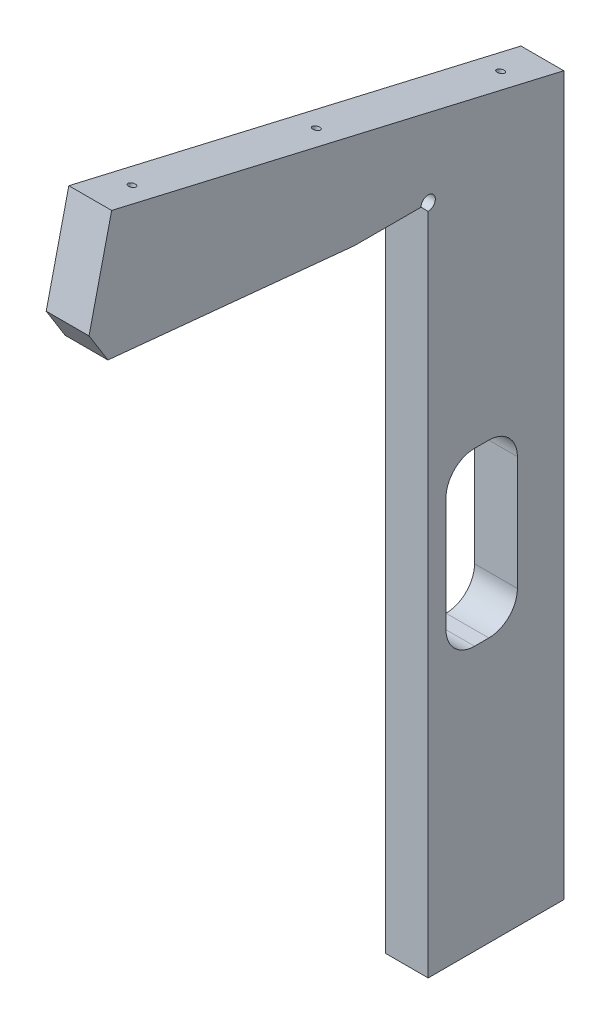
SolidWorks part; units mm, degrees
material "MDF"
ref_plane "Front Plane" through (0, 0, 0) normal (0, 0, 1) x (1, 0, 0)
ref_plane "Top Plane" through (0, 0, 0) normal (0, 1, 0) x (1, 0, 0)
ref_plane "Right Plane" through (0, 0, 0) normal (1, 0, 0) x (0, 0, -1)
sketch "Sketch2" plane through (-113.7888, 0, 0) normal (1, 0, 0) x (0, 0, -1)
  line L17 (0, 20.8246) -> (-83.8286, 40.3069)
  line L18 (0, 20.8246) -> (-83.8286, 40.3069)
  line L29 (-83.8286, 40.3069) -> (-93.1962, 0)
  line L30 (-83.8286, 40.3069) -> (-93.1962, 0)
  line L31 (-93.1962, 0) -> (-63.5, 0)
  line L32 (-93.1962, 0) -> (-63.5, 0)
  line L46 (0, -298.45) -> (-60.325, -298.45)
  line L47 (0, -392.9838) -> (0, -398.937) construction
  line L48 (-28.575, -298.45) -> (0, -298.45) construction
  line L53 (-8.8658, -437.642) -> (0, -437.642)
  line L55 (0, -437.642) -> (0, 20.8246)
  line L57 (-60.325, -3.175) -> (-60.325, -412.75)
  line L60 (0, -298.45) -> (0, 20.8246)
  line L62 (-60.325, -3.175) -> (-60.325, -298.45)
  arc A14 (-60.325, -3.175) -> (-63.5, 0) centre (-60.325, 0) ccw
  arc A15 (-60.325, -412.75) -> (-8.8658, -437.642) centre (-28.575, -412.75) ccw
  arc A17 (-60.325, -3.175) -> (-63.5, 0) centre (-60.325, 0) ccw
  dimension "D2" = 0
extrude "Boss-Extrude1" add sketch "Sketch2" along normal blind 19.05
sketch "Sketch3" plane through (-113.7888, 0, 0) normal (-1, 0, 0) x (0, 0, 1)
  line L0 (83.8286, 40.3069) -> (201.0857, 67.5582)
  line L1 (495.3358, 135.9439) -> (66.675, 36.3203) construction
  line L2 (201.0857, 67.5582) -> (214.0229, 11.8918)
  line L7 (83.8286, 40.3069) -> (93.1962, 0)
  line L8 (93.1962, 0) -> (214.0229, 11.8918)
  arc A0 (63.5, 0) -> (60.325, -3.175) centre (60.325, 0) ccw construction
  dimension "D1" = 57.15
  dimension "D2" = 152.4
extrude "Boss-Extrude2" add sketch "Sketch3" against normal through all
chamfer "Chamfer1" distance 12.7 angle 45 1 edges at (-104.2638, 11.8918, 214.0229) first distance on face at (-104.2638, 39.725, 207.5543)
hole_wizard "Hole3" positions "Sketch8" profile "Sketch9" legacy
sketch "Sketch8" plane through (0, 45.0826, -35.8775) normal (0, 0.974, -0.2264) x (-1, 0, 0)
  line L0 (218.5638, 29.4548) -> (218.5638, 115.5175) construction
  line L4 (202.6895, 537.9919) -> (202.6895, 97.9067) construction
  line L9 (88.3895, 537.9919) -> (88.3895, 97.9067) construction
  line L13 (104.2638, 29.4548) -> (104.2638, 235.8996) construction
  line L16 (0, 537.9919) -> (0, 29.4548) construction
  point P0 (218.5638, 102.8175)
  point P2 (218.5638, 48.5048)
  point P33 (202.6895, 123.3067)
  point P35 (202.6895, 317.9493)
  point P37 (202.6895, 518.9419)
  point P51 (88.3895, 518.9419)
  point P53 (88.3895, 317.9493)
  point P55 (88.3895, 123.3067)
  point P69 (104.2638, 216.8496)
  point P71 (104.2638, 132.6772)
  point P73 (104.2638, 48.5048)
  point P83 (-104.2638, 48.5048)
  point P84 (-104.2638, 132.6772)
  point P85 (-104.2638, 216.8496)
  point P86 (-88.3895, 123.3067)
  point P87 (-88.3895, 317.9493)
  point P88 (-88.3895, 518.9419)
  point P89 (-202.6895, 518.9419)
  point P90 (-202.6895, 317.9493)
  point P91 (-202.6895, 123.3067)
  point P92 (-218.5638, 48.5048)
  point P93 (-218.5638, 102.8175)
sketch "Sketch9" plane through (-218.5638, 68.3578, 64.2709) normal (1, 0, 0) x (0, 0.2264, 0.974)
  line L0 (0, 0) -> (0, 51.7539)
  line L1 (0, 51.7539) -> (1.5875, 50.8)
  line L2 (1.5875, 50.8) -> (1.5875, 4.0177)
  line L3 (1.5875, 4.0177) -> (5.08, 0)
  line L4 (5.08, 0) -> (0, 0)
  line L5 (0, -14.3089) -> (0, 102.4216) construction
  line L6 (0, 51.7539) -> (-1.5875, 50.8) construction
  line L7 (-1.5875, 4.0177) -> (-5.08, 0) construction
  dimension "Diameter" = 3.175
  dimension "Depth" = 50.8
  dimension "C-Sink Diameter" = 10.16
  dimension "C-Sink Angle" = 82
  dimension "Drill Angle" = 118
hole_wizard "Hole4" positions "Sketch10" profile "Sketch11" legacy
sketch "Sketch10" plane through (0, 0, -25.4) normal (0, 0, -1) x (-1, 0, 0)
  line L0 (218.5638, 0) -> (218.5638, -437.642) construction
  line L4 (104.2638, 0) -> (104.2638, -298.45) construction
  line L13 (120.1388, -460.375) -> (120.1388, -311.15) construction
  line L16 (126.4888, -311.15) -> (113.7888, -311.15) construction
  line L18 (126.4888, -304.8) -> (-126.4888, -304.8) construction
  line L22 (94.7388, -276.225) -> (-94.7388, -276.225) construction
  line L24 (-94.7388, -285.75) -> (-94.7388, -266.7) construction
  line L26 (94.7388, -285.75) -> (94.7388, -266.7) construction
  line L27 (-94.7388, 0) -> (-94.7388, -19.05) construction
  line L29 (94.7388, 0) -> (94.7388, -19.05) construction
  line L31 (94.7388, -9.525) -> (-94.7388, -9.525) construction
  point P15 (218.5638, -31.75)
  point P17 (218.5638, -218.821)
  point P19 (218.5638, -418.592)
  point P28 (104.2638, -19.05)
  point P30 (104.2638, -149.225)
  point P32 (104.2638, -279.4)
  point P69 (120.1388, -330.2)
  point P71 (120.1388, -441.325)
  point P76 (-120.1388, -441.325)
  point P77 (-120.1388, -330.2)
  point P80 (-104.2638, -279.4)
  point P81 (-104.2638, -149.225)
  point P82 (-104.2638, -19.05)
  point P83 (-218.5638, -418.592)
  point P84 (-218.5638, -218.821)
  point P85 (-218.5638, -31.75)
  point P99 (0, -304.8)
  point P101 (107.4388, -304.8)
  point P103 (-107.4388, -304.8)
  point P127 (75.6888, -276.225)
  point P129 (0, -276.225)
  point P131 (-75.6888, -276.225)
  point P152 (75.6888, -9.525)
  point P154 (0, -9.525)
  point P156 (-75.6888, -9.525)
  point P158 (0, 0)
sketch "Sketch11" plane through (75.6888, -9.525, -25.4) normal (1, 0, 0) x (0, 1, 0)
  line L0 (0, 0) -> (0, 39.0539)
  line L1 (0, 39.0539) -> (1.5875, 38.1)
  line L2 (1.5875, 38.1) -> (1.5875, 4.0177)
  line L3 (1.5875, 4.0177) -> (5.08, 0)
  line L4 (5.08, 0) -> (0, 0)
  line L5 (0, -14.3089) -> (0, 102.4216) construction
  line L6 (0, 39.0539) -> (-1.5875, 38.1) construction
  line L7 (-1.5875, 4.0177) -> (-5.08, 0) construction
  dimension "Diameter" = 3.175
  dimension "Depth" = 38.1
  dimension "C-Sink Diameter" = 10.16
  dimension "C-Sink Angle" = 82
  dimension "Drill Angle" = 118
sketch "Sketch12" plane through (-94.7388, 0, 0) normal (1, 0, 0) x (0, 0, -1)
  line L0 (-30.1625, -19.05) -> (-30.1625, -266.7) construction
  line L1 (-60.325, -19.05) -> (0, -19.05) construction
  line L2 (-60.325, -266.7) -> (0, -266.7) construction
  line L4 (-52.3875, -180.975) -> (-20.6375, -180.975)
  line L5 (-52.3875, -180.975) -> (-52.3875, -104.775)
  line L6 (-52.3875, -104.775) -> (-20.6375, -104.775)
  line L7 (-20.6375, -180.975) -> (-20.6375, -104.775)
  line L8 (-52.3875, -180.975) -> (-20.6375, -104.775) construction
  line L9 (-52.3875, -104.775) -> (-20.6375, -180.975) construction
  point P6 (-36.5125, -142.875)
  point P12 (-30.1625, -142.875)
  dimension "D1" = 31.75
  dimension "D2" = 76.2
  dimension "D3" = 6.35
extrude "Cut-Extrude1" cut sketch "Sketch12" against normal through all
fillet "Fillet1" radius 12.7 4 edges at (-104.2638, -180.975, 52.3875) (-104.2638, -104.775, 52.3875) (-104.2638, -180.975, 20.6375) (-104.2638, -104.775, 20.6375)
